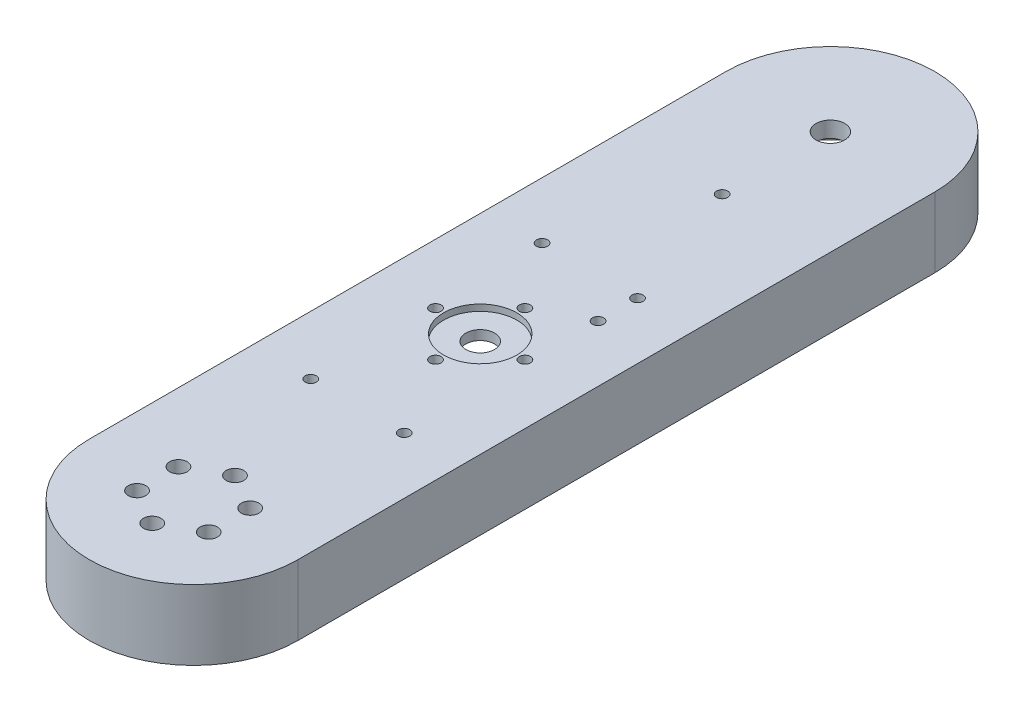
SolidWorks part; units mm, degrees
ref_plane "Front Plane" through (0, 0, 0) normal (0, 0, 1) x (1, 0, 0)
ref_plane "Top Plane" through (0, 0, 0) normal (0, 1, 0) x (1, 0, 0)
ref_plane "Right Plane" through (0, 0, 0) normal (1, 0, 0) x (0, 0, -1)
sketch "Sketch1" plane through (0, 0, 0) normal (0, 1, 0) x (1, 0, 0)
  line L5 (-32.774, -22.3805) -> (-32.774, 177.6195)
  line L6 (32.774, -22.3805) -> (32.774, 177.6195)
  circle A3 centre (0, 177.6195) radius 4.5
  circle A4 centre (0, 67.6378) radius 4.5
  circle A5 centre (15, 89.6378) radius 1.75
  circle A7 centre (-6.7334, 37.1195) radius 1.25
  circle A8 centre (-6.7334, 27.6195) radius 1.25
  circle A14 centre (0, 53.6052) radius 1.75
  circle A15 centre (-14.0327, 67.6378) radius 1.75
  circle A16 centre (0, 81.6705) radius 1.75
  circle A17 centre (14.0327, 67.6378) radius 1.75
  circle A18 centre (0, 67.6378) radius 11.5
  circle A19 centre (0, 67.6378) radius 4.5
  arc A22 (32.774, -22.3805) -> (-32.774, -22.3805) centre (0, -22.3805) cw
  arc A23 (32.774, 177.6195) -> (-32.774, 177.6195) centre (0, 177.6195) ccw
  circle A25 centre (0, -9.3805) radius 2.75
  circle A27 centre (11.2583, -15.8805) radius 2.75
  circle A28 centre (11.2583, -28.8805) radius 2.75
  circle A29 centre (0, -35.3805) radius 2.75
  circle A30 centre (-11.2583, -28.8805) radius 2.75
  circle A31 centre (-11.2583, -15.8805) radius 2.75
  dimension "D1" = 13
  dimension "D2" = 200
  dimension "D3" = 50
  dimension "D4" = 109.9817
  dimension "D5" = 22
  dimension "D8" = 9.5
  dimension "D6" = 15
extrude "Boss-Extrude10" add sketch "Sketch1" against normal blind 5 contours L6 A23 L5 A22 A31 A30 A29 A28 A27 A25 A3 A5 A7 A8 A14 A15 A16 A17 A18 | A18 | A19 region at (-30.0388, 0, -77.6195)
sketch "Sketch2" plane through (0, 0, 0) normal (0, -1, 0) x (1, 0, 0)
  line L30 (28, -177.6198) -> (28, -97.6193)
  line L35 (-28, -177.6198) -> (-28, -97.62)
  line L46 (-28, -4.769) -> (28, -4.769)
  line L54 (-32.774, 22.3805) -> (-32.774, -177.6198)
  line L55 (32.774, 22.3805) -> (32.774, -177.6198)
  line L56 (-28, 22.3805) -> (-28, -97.62)
  line L57 (28, -97.6193) -> (28, 22.3805)
  circle A4 centre (-18, -157.4003) radius 1.75
  circle A5 centre (18.0605, -157.4003) radius 1.75
  circle A6 centre (-18, -97.6199) radius 1.75
  circle A7 centre (18.0032, -97.4003) radius 1.75
  arc A15 (28, -177.6198) -> (-28, -177.6198) centre (0, -177.6198) cw
  arc A26 (32.774, 22.3805) -> (-32.774, 22.3805) centre (0, 22.3805) ccw
  arc A28 (-32.774, -177.6198) -> (32.774, -177.6198) centre (0, -177.6198) ccw
  arc A29 (28, 22.3805) -> (-28, 22.3805) centre (0, 22.3805) ccw
  dimension "D1" = 60
extrude "Boss-Extrude9" add sketch "Sketch2" along normal blind 22 contours A29 L57 L30 A15 L35 L56 region at (0, 0, 52.4193)
extrude "Cut-Extrude3" cut sketch "Sketch1<14>" against normal blind 2 contours A18 A4 region at (-11.1747, 0, -67.6378)
sketch "Sketch1<14>" plane through (0, 0, 0) normal (0, 1, 0) x (1, 0, 0) same geometry as "Sketch1"
extrude "Boss-Extrude11" add sketch "Sketch1<16>" against normal blind 5 contours A7 | A8 region at (-6.7334, 0, -37.1195) region at (-6.7334, 0, -27.6195)
sketch "Sketch1<16>" plane through (0, 0, 0) normal (0, 1, 0) x (1, 0, 0) same geometry as "Sketch1"
extrude "Boss-Extrude12" add sketch "Sketch2<13>" along normal blind 22 contours L57 A29 L56 region at (0, 0, 20.1987)
sketch "Sketch2<13>" plane through (0, 0, 0) normal (0, -1, 0) x (1, 0, 0) same geometry as "Sketch2"
extrude "Cut-Extrude4" cut sketch "Sketch1<17>" against normal blind 55 contours A30 | A29 | A31 | A25 | A27 | A28 region at (0, 0, 9.3805) region at (11.2583, 0, 15.8805) region at (11.2583, 0, 28.8805) region at (0, 0, 35.3805) region at (-11.2583, 0, 28.8805) region at (-11.2583, 0, 15.8805)
sketch "Sketch1<17>" plane through (0, 0, 0) normal (0, 1, 0) x (1, 0, 0) same geometry as "Sketch1"
sketch "Sketch3" plane through (0, -5, 0) normal (0, -1, 0) x (1, 0, 0)
  line L0 (-28, -177.6198) -> (-28, -4.769) construction
  line L1 (28, -177.6198) -> (28, -4.769) construction
  line L3 (-28, -4.769) -> (28, -4.769) construction
  circle A0 centre (15, -89.6378) radius 1.75
  circle A1 centre (15, -28.769) radius 1.75
  circle A2 centre (-14.3535, -28.769) radius 1.75
  circle A3 centre (-15, -102.0563) radius 1.75
  circle A4 centre (15, -102.0563) radius 1.75
  circle A5 centre (0, -143.6198) radius 1.75
  arc A6 (-28, -177.6198) -> (28, -177.6198) centre (0, -177.6198) ccw construction
  dimension "D1" = 34
  dimension "D2" = 13
  dimension "D3" = 13
  dimension "D4" = 24
  dimension "D5" = 24
extrude "Cut-Extrude5" cut sketch "Sketch3" against normal blind 17
